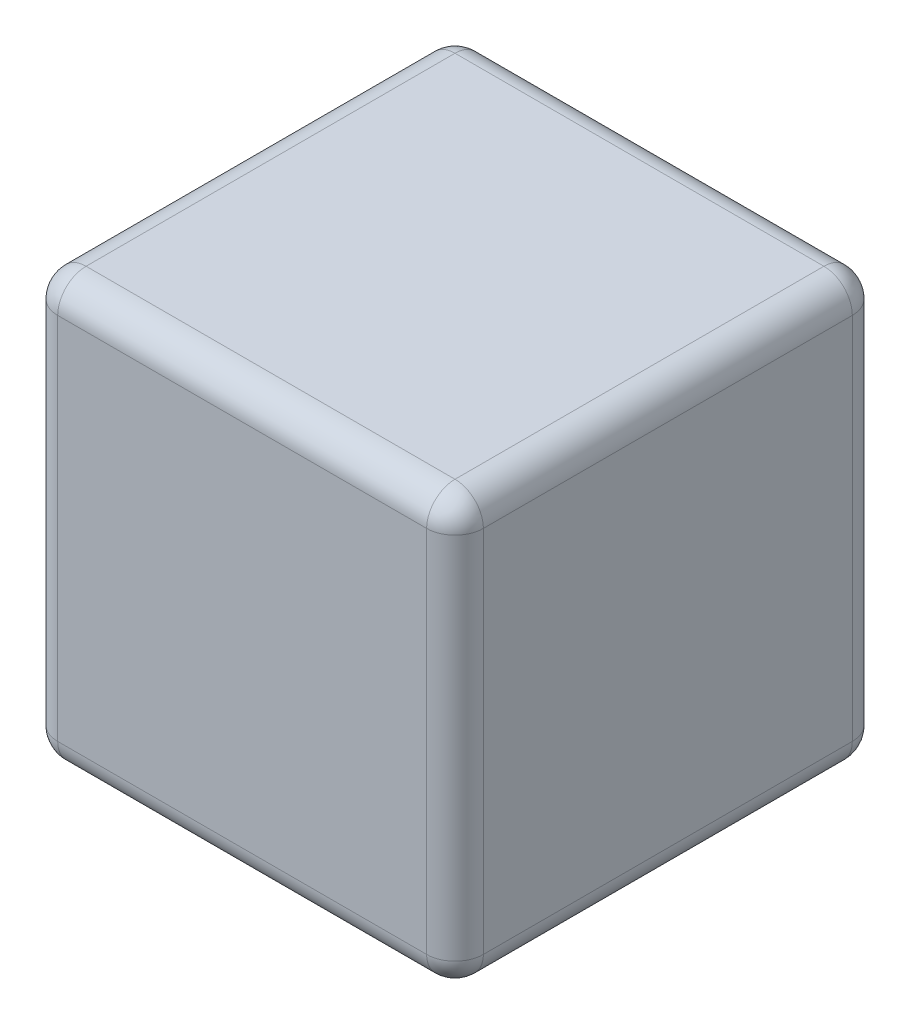
SolidWorks part; units mm, degrees
ref_plane "Front Plane" through (0, 0, 0) normal (0, 0, 1) x (1, 0, 0)
ref_plane "Top Plane" through (0, 0, 0) normal (0, 1, 0) x (1, 0, 0)
ref_plane "Right Plane" through (0, 0, 0) normal (1, 0, 0) x (0, 0, -1)
sketch "Sketch1" plane through (0, 0, 0) normal (0, 1, 0) x (1, 0, 0)
  line L1 (-19.05, 19.05) -> (19.05, 19.05)
  line L2 (-19.05, 19.05) -> (-19.05, -19.05)
  line L3 (-19.05, -19.05) -> (19.05, -19.05)
  line L4 (19.05, 19.05) -> (19.05, -19.05)
  line L5 (-19.05, 19.05) -> (19.05, -19.05) construction
  line L6 (-19.05, -19.05) -> (19.05, 19.05) construction
  point P0 (0, 0)
  dimension "D1" = 38.1
  dimension "D2" = 38.1
extrude "Boss-Extrude1" add sketch "Sketch1" along normal blind 38.1
fillet "Fillet1" radius 2.54 12 edges at (-19.05, 0, 0) (-19.05, 19.05, -19.05) (0, 0, -19.05) (19.05, 19.05, -19.05) (19.05, 0, 0) (-19.05, 38.1, 0) (0, 38.1, -19.05) (19.05, 38.1, 0) (-19.05, 19.05, 19.05) (0, 38.1, 19.05) (19.05, 19.05, 19.05) (0, 0, 19.05)
